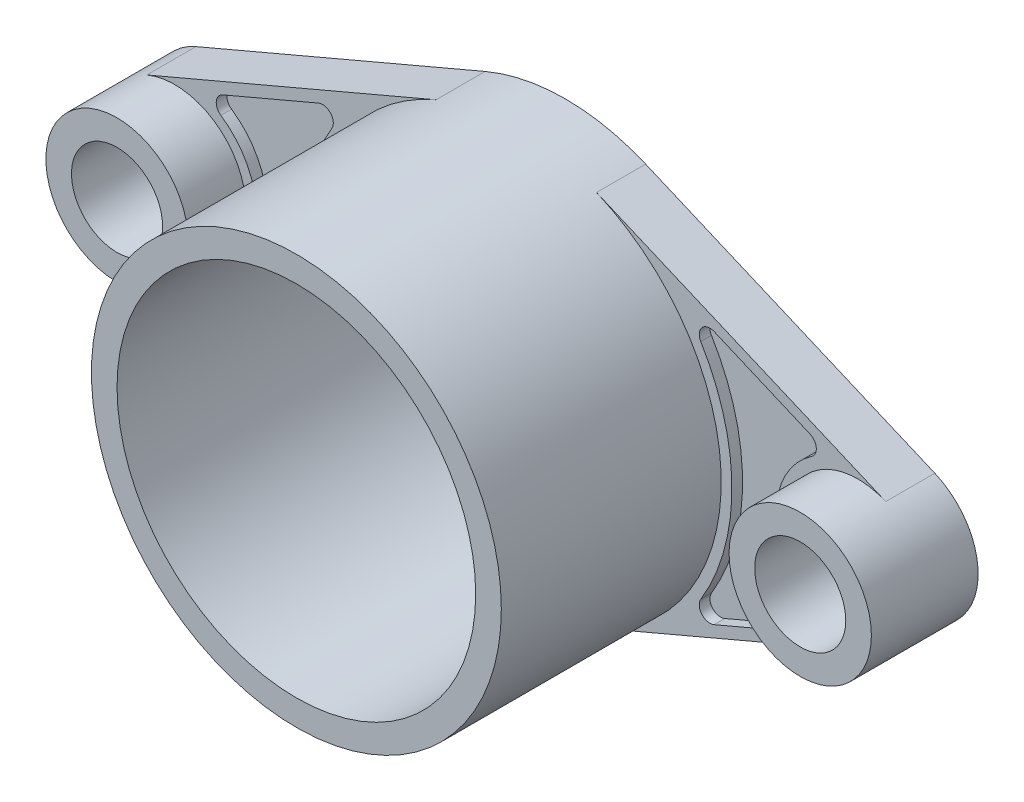
SolidWorks part; units mm, degrees
material "Polybutadiene (PB)"
ref_plane "Front Plane" through (0, 0, 0) normal (0, 0, 1) x (1, 0, 0)
ref_plane "Top Plane" through (0, 0, 0) normal (0, 1, 0) x (1, 0, 0)
ref_plane "Right Plane" through (0, 0, 0) normal (1, 0, 0) x (0, 0, -1)
sketch "Sketch1" plane through (0, 0, 0) normal (0, 0, 1) x (1, 0, 0)
  line L0 (0, 0) -> (80, 0) construction
  line L1 (0, 48) -> (0, -48) construction
  line L2 (18.8, -44.1651) -> (86.5278, -15.3351)
  line L3 (18.8, 44.1651) -> (86.5278, 15.3351)
  line L4 (-18.8, -44.1651) -> (-86.5278, -15.3351)
  line L5 (-18.8, 44.1651) -> (-86.5278, 15.3351)
  circle A0 centre (0, 0) radius 42
  circle A1 centre (0, 0) radius 48
  circle A2 centre (80, 0) radius 10.6667
  circle A3 centre (80, 0) radius 16.6667
  circle A4 centre (-80, 0) radius 10.6667
  circle A5 centre (-80, 0) radius 16.6667
  dimension "D3" = 96
  dimension "D5" = 21.3333
  dimension "D1" = 6
  dimension "D2" = 6
  dimension "D4" = 160
extrude "Boss-Extrude1" add sketch "Sketch1" along normal blind 11.5 contours L5 A5 L4 A1 | A3 L3 A1 L2 region at (54.8023, 0, 0) region at (-54.8023, 0, 0)
sketch "Sketch2" plane through (0, 0, 11.5) normal (0, 0, 1) x (1, 0, 0)
  line L2 (-63.3333, 0) -> (-48, 0) construction
  line L4 (-37.9794, 33.2839) -> (-73.6701, 18.0912)
  line L5 (-73.6701, -18.0912) -> (-37.9794, -33.2839)
  line L6 (-46.3293, 29.7295) -> (-68.7498, 20.1857)
  line L7 (-68.7498, -20.1857) -> (-46.3293, -29.7295)
  arc A2 (-69.1817, -15.8217) -> (-68.7498, -20.1857) centre (-67.7707, -17.8854) ccw
  arc A3 (-86.5278, -15.3351) -> (-86.5278, 15.3351) centre (-80, 0) ccw construction
  arc A4 (-73.6701, -18.0912) -> (-73.6701, 18.0912) centre (-80, 0) ccw
  arc A5 (-37.9794, 33.2839) -> (-37.9794, -33.2839) centre (0, 0) ccw
  arc A6 (-69.1817, -15.8217) -> (-69.1817, 15.8217) centre (-80, 0) ccw
  arc A7 (-43.211, 26.1354) -> (-43.211, -26.1354) centre (0, 0) ccw
  arc A8 (-18.8, 44.1651) -> (-18.8, -44.1651) centre (0, 0) ccw construction
  arc A9 (-69.1817, 15.8217) -> (-68.7498, 20.1857) centre (-67.7707, 17.8854) cw
  arc A10 (-46.3293, -29.7295) -> (-43.211, -26.1354) centre (-45.3501, -27.4293) ccw
  arc A11 (-46.3293, 29.7295) -> (-43.211, 26.1354) centre (-45.3501, 27.4293) cw
  dimension "D2" = 2.5
  dimension "D3" = 2.5
  dimension "D1" = 2.5
extrude "Cut-Extrude1" cut sketch "Sketch2" against normal blind 2.5
mirror "Mirror1" about plane through (0, 0, 0) normal (1, 0, 0) of "Cut-Extrude1"
extrude "Boss-Extrude2" add sketch "Sketch1<4>" along normal blind 25 contours A5 A4 | A3 A2 region at (63.8047, 0, 0) region at (-96.1953, 0, 0)
sketch "Sketch1<4>" plane through (0, 0, 0) normal (0, 0, 1) x (1, 0, 0) same geometry as "Sketch1"
extrude "Boss-Extrude3" add sketch "Sketch1<5>" along normal blind 63 contours A1 A0 region at (0, -46.6424, 0)
sketch "Sketch1<5>" plane through (0, 0, 0) normal (0, 0, 1) x (1, 0, 0) same geometry as "Sketch1"
equation "\"A\" = 32"
equation "\"B\" = 6"
equation "\"C\"= 2.5"
equation "\"D1@Sketch1\"=\"B\""
equation "\"D2@Sketch1\"=\"B\""
equation "\"D3@Sketch1\"=\"A\"*3"
equation "\"D4@Sketch1\"=\"A\"*5"
equation "\"D5@Sketch1\"=\"A\"*2/3"
equation "\"D1@Boss-Extrude1\"=\"C\"+9"
equation "\"D1@Sketch2\"=\"C\""
equation "\"D2@Sketch2\"=\"C\""
equation "\"D3@Sketch2\"=\"C\""
equation "\"D1@Cut-Extrude1\"=\"C\""
